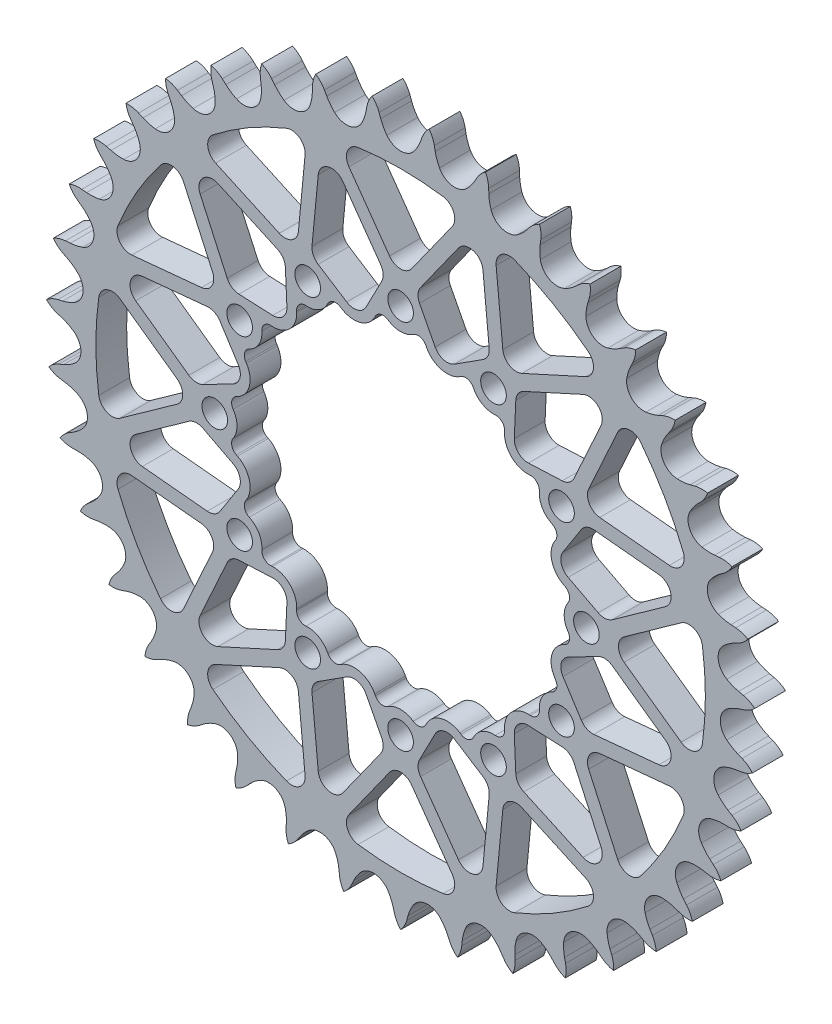
SolidWorks part; units mm, degrees
material "7075-T6 (SN)"
ref_plane "Front Plane" through (0, 0, 0) normal (0, 0, 1) x (1, 0, 0)
ref_plane "Top Plane" through (0, 0, 0) normal (0, 1, 0) x (1, 0, 0)
ref_plane "Right Plane" through (0, 0, 0) normal (1, 0, 0) x (0, 0, -1)
sketch "Work Sketch" plane through (0, 0, 0) normal (0, 0, 1) x (1, 0, 0)
  line L0 (0, 0) -> (0, 160.4542) construction
  line L1 (-112.0919, 78.9148) -> (87.2579, 78.9148) construction
  line L2 (5.102, 120.8822) -> (5.102, 112.9699) construction
  line L3 (-12.8497, 82.6953) -> (16.7256, 82.6953) construction
  line L4 (5.102, 82.6953) -> (-6.0879, 74.4036) construction
  line L5 (5.102, 82.6953) -> (-4.6505, 79.1506) construction
  line L6 (-4.6505, 79.1506) -> (-6.8863, 85.3019)
  line L7 (-11.5114, 78.0206) -> (-7.1525, 78.0206) construction
  line L8 (-11.0765, 124.7602) -> (-11.0765, 110.2345) construction
  line L9 (0, 0) -> (-3.4402, 42.6146) construction
  circle A0 centre (0, 0) radius 78.9148
  circle A1 centre (0, 78.9148) radius 4.0088
  arc A2 (-4.6505, 79.1506) -> (-3.2209, 76.5281) centre (5.0804, 82.7541) ccw
  circle A3 centre (-11.0765, 78.0206) radius 6.4254
  point P23 (-3.2209, 76.5281)
  dimension "D1" = 157.8295
  dimension "D8" = 10.3767
  dimension "D2" = 8.0177
  dimension "D3" = 5.102
  dimension "D4" = 3.7806
  dimension "D5" = 36.538
  dimension "D6" = 16.564
  dimension "D7" = 10.3767
  dimension "D9" = 0.8942
  dimension "D10" = 11.0765
  dimension "D11" = 4.615
sketch "Teeth Sketch" plane through (0, 0, 0) normal (0, 0, 1) x (1, 0, 0)
  line L0 (5.0376, 80.2155) -> (4.6505, 79.1506)
  line L1 (-7.4865, 92.7372) -> (-4.7839, 59.2593) construction
  line L2 (0, 0) -> (-10.9133, 132.3061) construction
  line L3 (7.8951, 79.9848) -> (8.1063, 78.8717)
  line L4 (16093.3137, -199351.4616) -> (-16096.7539, 199394.0762) construction
  line L5 (0, 146.3285) -> (0, 56.9858) construction
  line L6 (17.8398, 78.3686) -> (17.287, 77.3797)
  line L7 (0, -200000) -> (0, 200160.4542) construction
  line L8 (20.6234, 77.6826) -> (20.6533, 76.5499)
  line L9 (-4.6505, 79.1506) -> (-6.8863, 85.3019) construction
  line L10 (44.1616, 67.154) -> (43.8313, 66.0702)
  line L11 (-5.0376, 80.2155) -> (-4.6505, 79.1506)
  line L12 (30.18, 74.4921) -> (29.4757, 73.6046)
  line L13 (32.8175, 73.3684) -> (32.6653, 72.2456)
  line L14 (41.7385, 68.6862) -> (40.901, 67.9232)
  line L15 (52.2161, 61.1014) -> (51.267, 60.4826)
  line L16 (54.362, 59.2003) -> (53.8621, 58.1836)
  line L17 (61.3413, 51.9341) -> (60.3052, 51.4756)
  line L18 (63.1544, 49.7134) -> (62.4979, 48.79)
  line L19 (68.8777, 41.4218) -> (67.7815, 41.1354)
  line L20 (70.3112, 38.939) -> (69.515, 38.1328)
  line L21 (74.6303, 29.8366) -> (73.5023, 29.7298)
  line L22 (75.6469, 27.156) -> (74.7318, 26.488)
  line L23 (78.45, 17.4787) -> (77.3195, 17.5542)
  line L24 (79.0234, 14.6698) -> (78.013, 14.1572)
  line L25 (80.2378, 4.6681) -> (79.1341, 4.9239)
  line L26 (80.3533, 1.8035) -> (79.2737, 1.4597)
  line L27 (79.9476, -8.2634) -> (78.8992, -7.8338)
  line L28 (79.602, -11.1094) -> (78.4813, -11.2756)
  line L29 (77.5867, -20.9809) -> (76.6208, -20.3887)
  line L30 (76.7891, -23.7346) -> (75.6562, -23.7189)
  line L31 (73.2164, -33.155) -> (72.358, -32.4155)
  line L32 (71.9874, -35.7451) -> (70.8717, -35.5478)
  line L33 (66.9499, -44.4704) -> (66.2212, -43.6028)
  line L34 (65.3213, -46.8298) -> (64.2517, -46.4561)
  line L35 (58.9493, -54.634) -> (58.3693, -53.6608)
  line L36 (56.9634, -56.7016) -> (55.9676, -56.1612)
  line L37 (49.422, -63.3827) -> (49.0056, -62.329)
  line L38 (47.1301, -65.1049) -> (46.2339, -64.4118)
  line L39 (38.6147, -70.4897) -> (38.3727, -69.3829)
  line L40 (36.0763, -71.822) -> (35.3028, -70.9941)
  line L41 (26.8073, -75.7712) -> (26.746, -74.6398)
  line L42 (24.088, -76.679) -> (23.4574, -75.7377)
  line L43 (14.3056, -79.0901) -> (14.4266, -77.9636)
  line L44 (11.4759, -79.55) -> (11.0044, -78.5198)
  line L45 (1.4334, -80.3607) -> (1.7335, -79.2682)
  line L46 (-1.4334, -80.3607) -> (-1.7335, -79.2682)
  line L47 (-11.4759, -79.55) -> (-11.0044, -78.5198)
  line L48 (-14.3056, -79.0901) -> (-14.4266, -77.9636)
  line L49 (-24.088, -76.679) -> (-23.4574, -75.7377)
  line L50 (-26.8073, -75.7712) -> (-26.746, -74.6398)
  line L51 (-36.0763, -71.822) -> (-35.3028, -70.9941)
  line L52 (-38.6147, -70.4897) -> (-38.3727, -69.3829)
  line L53 (-47.1301, -65.1049) -> (-46.2339, -64.4118)
  line L54 (-49.422, -63.3827) -> (-49.0056, -62.329)
  line L55 (-56.9634, -56.7016) -> (-55.9676, -56.1612)
  line L56 (-58.9493, -54.634) -> (-58.3693, -53.6608)
  line L57 (-65.3213, -46.8298) -> (-64.2517, -46.4561)
  line L58 (-66.9499, -44.4704) -> (-66.2212, -43.6028)
  line L59 (-71.9874, -35.7451) -> (-70.8717, -35.5478)
  line L60 (-73.2164, -33.155) -> (-72.358, -32.4155)
  line L61 (-76.7891, -23.7346) -> (-75.6562, -23.7189)
  line L62 (-77.5867, -20.9809) -> (-76.6208, -20.3887)
  line L63 (-79.602, -11.1094) -> (-78.4813, -11.2756)
  line L64 (-79.9476, -8.2634) -> (-78.8992, -7.8338)
  line L65 (-80.3533, 1.8035) -> (-79.2737, 1.4597)
  line L66 (-80.2378, 4.6681) -> (-79.1341, 4.9239)
  line L67 (-79.0234, 14.6698) -> (-78.013, 14.1572)
  line L68 (-78.45, 17.4787) -> (-77.3195, 17.5542)
  line L69 (-75.6469, 27.156) -> (-74.7318, 26.488)
  line L70 (-74.6303, 29.8366) -> (-73.5023, 29.7298)
  line L71 (-70.3112, 38.939) -> (-69.515, 38.1328)
  line L72 (-68.8777, 41.4218) -> (-67.7815, 41.1354)
  line L73 (-63.1544, 49.7134) -> (-62.4979, 48.79)
  line L74 (-61.3413, 51.9341) -> (-60.3052, 51.4756)
  line L75 (-54.362, 59.2003) -> (-53.8621, 58.1836)
  line L76 (-52.2161, 61.1014) -> (-51.267, 60.4826)
  line L77 (-44.1616, 67.154) -> (-43.8313, 66.0702)
  line L78 (-41.7385, 68.6862) -> (-40.901, 67.9232)
  line L79 (-32.8175, 73.3684) -> (-32.6653, 72.2456)
  line L80 (-30.18, 74.4921) -> (-29.4757, 73.6046)
  line L81 (-20.6234, 77.6826) -> (-20.6533, 76.5499)
  line L82 (-17.8398, 78.3686) -> (-17.287, 77.3797)
  line L83 (-7.8951, 79.9848) -> (-8.1063, 78.8717)
  arc A0 (-6.8336, 82.8459) -> (-5.0376, 80.2155) centre (-11.0765, 78.0206) cw
  circle A1 centre (-11.0765, 78.0206) radius 6.4254 construction
  arc A2 (-3.2209, 76.5281) -> (-4.6505, 79.1506) centre (5.0804, 82.7541) cw
  arc A3 (-4.6505, 79.1506) -> (-3.2209, 76.5281) centre (5.0804, 82.7541) ccw construction
  circle A4 centre (0, 78.9148) radius 4.0088 construction
  arc A5 (-3.2209, 76.5281) -> (3.2209, 76.5281) centre (0, 78.9148) ccw
  arc A6 (3.2209, 76.5281) -> (4.6505, 79.1506) centre (-5.0804, 82.7541) ccw
  arc A7 (6.8336, 82.8459) -> (5.0376, 80.2155) centre (11.0765, 78.0206) ccw
  arc A8 (6.5443, 82.8692) -> (7.8951, 79.9848) centre (1.5824, 78.787) cw
  arc A9 (9.0967, 76.0537) -> (8.1063, 78.8717) centre (18.2893, 80.8676) cw
  arc A10 (9.0967, 76.0537) -> (15.4552, 75.0204) centre (12.6588, 77.8928) ccw
  arc A11 (15.4552, 75.0204) -> (17.287, 77.3797) centre (8.2601, 82.4975) ccw
  arc A12 (20.0345, 80.6769) -> (17.8398, 78.3686) centre (23.4484, 75.2334) ccw
  arc A13 (19.7528, 80.7463) -> (20.6234, 77.6826) centre (14.2002, 77.5129) cw
  arc A14 (21.1788, 73.6096) -> (20.6533, 76.5499) centre (31.0245, 76.8865) cw
  arc A15 (21.1788, 73.6096) -> (27.2892, 71.5697) centre (24.9898, 74.8535) ccw
  arc A16 (27.2892, 71.5697) -> (29.4757, 73.6046) centre (21.3867, 80.1041) ccw
  arc A17 (32.7165, 76.4184) -> (30.18, 74.4921) centre (35.2131, 70.4978) ccw
  arc A18 (32.4496, 76.5321) -> (32.8175, 73.3684) centre (26.4502, 74.2313) cw
  arc A19 (32.7124, 69.2591) -> (32.6653, 72.2456) centre (42.9562, 70.9142) cw
  arc A20 (32.7124, 69.2591) -> (38.4163, 66.2654) centre (36.6735, 69.8756) ccw
  arc A21 (38.4163, 66.2654) -> (40.901, 67.9232) centre (33.9593, 75.6361) ccw
  arc A22 (44.5512, 70.1807) -> (41.7385, 68.6862) centre (46.0657, 63.9363) ccw
  arc A23 (44.306, 70.3358) -> (44.1616, 67.154) centre (38.0153, 69.0271) cw
  arc A24 (43.3987, 63.1147) -> (43.8313, 66.0702) centre (53.7754, 63.1052) cw
  arc A25 (43.3987, 63.1147) -> (48.5486, 59.2448) centre (47.4074, 63.0878) ccw
  arc A26 (48.5486, 59.2448) -> (51.267, 60.4826) centre (45.6524, 69.2092) ccw
  arc A27 (55.2321, 62.1253) -> (52.2161, 61.1014) centre (55.7253, 55.7189) ccw
  arc A28 (55.0149, 62.3178) -> (54.362, 59.2003) centre (48.5957, 62.0351) cw
  arc A29 (52.961, 55.3358) -> (53.8621, 58.1836) centre (63.2018, 53.6618) cw
  arc A30 (52.961, 55.3358) -> (57.4234, 50.6899) centre (56.9135, 54.6662) ccw
  arc A31 (57.4234, 50.6899) -> (60.3052, 51.4756) centre (56.1632, 60.9898) ccw
  arc A32 (64.4824, 52.461) -> (61.3413, 51.9341) centre (63.9416, 46.0584) ccw
  arc A33 (64.2989, 52.6858) -> (63.1544, 49.7134) centre (57.9175, 53.4365) cw
  arc A34 (61.1517, 46.1237) -> (62.4979, 48.79) centre (70.9913, 42.8287) cw
  arc A35 (61.1517, 46.1237) -> (64.811, 40.8221) centre (64.9456, 44.8287) ccw
  arc A36 (64.811, 40.8221) -> (67.7815, 41.1354) centre (65.2193, 51.1908) ccw
  arc A37 (72.0627, 41.4379) -> (68.8777, 41.4218) centre (70.5018, 35.205) ccw
  arc A38 (71.9177, 41.6892) -> (70.3112, 38.939) centre (65.7393, 43.4539) cw
  arc A39 (67.7585, 35.717) -> (69.515, 38.1328) centre (76.9422, 30.8862) cw
  arc A40 (67.7585, 35.717) -> (70.5201, 29.8971) centre (71.2956, 33.8302) ccw
  arc A41 (70.5201, 29.8971) -> (73.5023, 29.7298) centre (72.5864, 40.0659) ccw
  arc A42 (77.7767, 29.3416) -> (74.6303, 29.8366) centre (75.2361, 23.4398) ccw
  arc A43 (77.6738, 29.6129) -> (75.6469, 27.156) centre (71.8585, 32.3458) cw
  arc A44 (72.6105, 24.3852) -> (74.7318, 26.488) centre (80.9003, 18.1439) cw
  arc A45 (72.6105, 24.3852) -> (74.4027, 18.1977) centre (75.7991, 21.9555) ccw
  arc A46 (74.4027, 18.1977) -> (77.3195, 17.5542) centre (78.0734, 27.9034) ccw
  arc A47 (81.4762, 16.4854) -> (78.45, 17.4787) centre (78.0218, 11.0675) ccw
  arc A48 (81.4182, 16.7697) -> (79.0234, 14.6698) centre (76.1166, 20.4) cw
  arc A49 (75.5818, 12.4219) -> (78.013, 14.1572) centre (82.7631, 4.9316) cw
  arc A50 (75.5818, 12.4219) -> (76.3583, 6.027) centre (78.3394, 9.5121) ccw
  arc A51 (76.3583, 6.027) -> (79.1341, 4.9239) centre (81.5384, 15.0182) ccw
  arc A52 (83.0656, 3.2022) -> (80.2378, 4.6681) centre (78.7868, -1.5914) ccw
  arc A53 (83.0539, 3.4922) -> (80.3533, 1.8035) centre (78.4033, 7.9259) cw
  arc A54 (76.5957, 0.1368) -> (79.2737, 1.4597) centre (82.4825, -8.4084) cw
  arc A55 (76.5957, 0.1368) -> (76.3363, -6.2998) centre (78.8508, -3.1776) ccw
  arc A56 (76.3363, -6.2998) -> (78.8992, -7.8338) centre (82.8916, 1.7441) ccw
  arc A57 (82.5035, -10.1639) -> (79.9476, -8.2634) centre (77.5113, -14.2091) ccw
  arc A58 (82.5385, -9.8758) -> (79.602, -11.1094) centre (78.6594, -4.7535) cw
  arc A59 (75.6257, -12.1517) -> (78.4813, -11.2756) centre (80.0655, -21.5307) cw
  arc A60 (75.6257, -12.1517) -> (74.3372, -18.4634) centre (77.3199, -15.785) ccw
  arc A61 (74.3372, -18.4634) -> (76.6208, -20.3887) centre (82.0979, -11.5753) ccw
  arc A62 (79.8047, -23.2668) -> (77.5867, -20.9809) centre (74.2283, -26.4587) ccw
  arc A63 (79.8855, -22.9881) -> (76.7891, -23.7346) centre (76.8783, -17.3098) cw
  arc A64 (72.6971, -24.1256) -> (75.6562, -23.7189) centre (75.5749, -34.0953) cw
  arc A65 (72.6971, -24.1256) -> (70.4128, -30.1488) centre (73.7866, -27.9836) ccw
  arc A66 (70.4128, -30.1488) -> (72.358, -32.4155) centre (79.178, -24.5948) ccw
  arc A67 (75.039, -35.7671) -> (73.2164, -33.155) centre (69.0227, -38.0232) ccw
  arc A68 (75.1634, -35.5049) -> (71.9874, -35.7451) centre (73.106, -29.4178) cw
  arc A69 (67.8857, -35.4746) -> (70.8717, -35.5478) centre (69.127, -45.7768) cw
  arc A70 (67.8857, -35.4746) -> (64.6648, -41.0534) centre (68.3422, -39.4574) ccw
  arc A71 (64.6648, -41.0534) -> (66.2212, -43.6028) centre (74.2074, -36.9773) ccw
  arc A72 (68.3299, -47.341) -> (66.9499, -44.4704) centre (62.0296, -48.6028) ccw
  arc A73 (68.4947, -47.1022) -> (65.3213, -46.8298) centre (67.4404, -40.7639) cw
  arc A74 (61.3161, -45.9049) -> (64.2517, -46.4561) centre (60.8887, -56.2728) cw
  arc A75 (61.3161, -45.9049) -> (57.2419, -50.8948) centre (61.1278, -49.9093) ccw
  arc A76 (57.2419, -50.8948) -> (58.3693, -53.6608) centre (67.3148, -48.4022) ccw
  arc A77 (59.851, -57.6888) -> (58.9493, -54.634) centre (53.4299, -57.9236) ccw
  arc A78 (60.052, -57.4796) -> (56.9634, -56.7016) centre (60.0281, -51.0542) cw
  arc A79 (53.1584, -55.1462) -> (55.9676, -56.1612) centre (51.0734, -65.3113) cw
  arc A80 (53.1584, -55.1462) -> (48.3366, -59.4179) centre (52.3302, -59.0685) ccw
  arc A81 (48.3366, -59.4179) -> (49.0056, -62.329) centre (58.6789, -58.5735) ccw
  arc A82 (49.822, -66.5425) -> (49.422, -63.3827) centre (43.4464, -65.7443) ccw
  arc A83 (50.054, -66.3682) -> (47.1301, -65.1049) centre (51.0611, -60.0222) cw
  arc A84 (43.6239, -62.9593) -> (46.2339, -64.4118) centre (39.9354, -72.6583) cw
  arc A85 (43.6239, -62.9593) -> (38.1793, -66.4022) centre (42.1772, -66.698) ccw
  arc A86 (38.1793, -66.4022) -> (38.3727, -69.3829) centre (48.5231, -67.2277) ccw
  arc A87 (38.5026, -73.6728) -> (38.6147, -70.4897) centre (32.3376, -71.8622) ccw
  arc A88 (38.7596, -73.538) -> (36.0763, -71.822) centre (40.7716, -67.4357) cw
  arc A89 (32.9596, -69.1417) -> (35.3028, -70.9941) centre (27.763, -78.1234) cw
  arc A90 (32.9596, -69.1417) -> (27.0333, -71.6667) centre (30.932, -72.6) ccw
  arc A91 (27.0333, -71.6667) -> (26.746, -74.6398) centre (37.1107, -74.1408) ccw
  arc A92 (26.1861, -78.8951) -> (26.8073, -75.7712) centre (20.3913, -76.1189) ccw
  arc A93 (26.4613, -78.8032) -> (24.088, -76.679) centre (29.4261, -73.1027) cw
  arc A94 (21.4417, -73.5335) -> (23.4574, -75.7377) centre (14.8716, -81.5653) cw
  arc A95 (21.4417, -73.5335) -> (15.187, -75.0751) centre (18.8855, -76.6216) ccw
  arc A96 (15.187, -75.0751) -> (14.4266, -77.9636) centre (24.7371, -79.1336) ccw
  arc A97 (13.1913, -82.0739) -> (14.3056, -79.0901) centre (7.9169, -78.4042) ccw
  arc A98 (13.4777, -82.0274) -> (11.4759, -79.55) centre (17.3186, -76.8763) cw
  arc A99 (9.3684, -76.0207) -> (11.0044, -78.5198) centre (1.595, -82.8946) cw
  arc A100 (9.3684, -76.0207) -> (2.9475, -76.5391) centre (6.35, -78.6589) ccw
  arc A101 (2.9475, -76.5391) -> (1.7335, -79.2682) centre (11.7228, -82.077) ccw
  arc A102 (-0.1451, -83.1271) -> (1.4334, -80.3607) centre (-4.7625, -78.6589) ccw
  arc A103 (0.1451, -83.1271) -> (-1.4334, -80.3607) centre (4.7625, -78.6589) cw
  arc A104 (-2.9475, -76.5391) -> (-1.7335, -79.2682) centre (-11.7228, -82.077) cw
  arc A105 (-2.9475, -76.5391) -> (-9.3684, -76.0207) centre (-6.35, -78.6589) ccw
  arc A106 (-9.3684, -76.0207) -> (-11.0044, -78.5198) centre (-1.595, -82.8946) ccw
  arc A107 (-13.4777, -82.0274) -> (-11.4759, -79.55) centre (-17.3186, -76.8763) ccw
  arc A108 (-13.1913, -82.0739) -> (-14.3056, -79.0901) centre (-7.9169, -78.4042) cw
  arc A109 (-15.187, -75.0751) -> (-14.4266, -77.9636) centre (-24.7371, -79.1336) cw
  arc A110 (-15.187, -75.0751) -> (-21.4417, -73.5335) centre (-18.8855, -76.6216) ccw
  arc A111 (-21.4417, -73.5335) -> (-23.4574, -75.7377) centre (-14.8716, -81.5653) ccw
  arc A112 (-26.4613, -78.8032) -> (-24.088, -76.679) centre (-29.4261, -73.1027) ccw
  arc A113 (-26.1861, -78.8951) -> (-26.8073, -75.7712) centre (-20.3913, -76.1189) cw
  arc A114 (-27.0333, -71.6667) -> (-26.746, -74.6398) centre (-37.1107, -74.1408) cw
  arc A115 (-27.0333, -71.6667) -> (-32.9596, -69.1417) centre (-30.932, -72.6) ccw
  arc A116 (-32.9596, -69.1417) -> (-35.3028, -70.9941) centre (-27.763, -78.1234) ccw
  arc A117 (-38.7596, -73.538) -> (-36.0763, -71.822) centre (-40.7716, -67.4357) ccw
  arc A118 (-38.5026, -73.6728) -> (-38.6147, -70.4897) centre (-32.3376, -71.8622) cw
  arc A119 (-38.1793, -66.4022) -> (-38.3727, -69.3829) centre (-48.5231, -67.2277) cw
  arc A120 (-38.1793, -66.4022) -> (-43.6239, -62.9593) centre (-42.1772, -66.698) ccw
  arc A121 (-43.6239, -62.9593) -> (-46.2339, -64.4118) centre (-39.9354, -72.6583) ccw
  arc A122 (-50.054, -66.3682) -> (-47.1301, -65.1049) centre (-51.0611, -60.0222) ccw
  arc A123 (-49.822, -66.5425) -> (-49.422, -63.3827) centre (-43.4464, -65.7443) cw
  arc A124 (-48.3366, -59.4179) -> (-49.0056, -62.329) centre (-58.6789, -58.5735) cw
  arc A125 (-48.3366, -59.4179) -> (-53.1584, -55.1462) centre (-52.3302, -59.0685) ccw
  arc A126 (-53.1584, -55.1462) -> (-55.9676, -56.1612) centre (-51.0734, -65.3113) ccw
  arc A127 (-60.052, -57.4796) -> (-56.9634, -56.7016) centre (-60.0281, -51.0542) ccw
  arc A128 (-59.851, -57.6888) -> (-58.9493, -54.634) centre (-53.4299, -57.9236) cw
  arc A129 (-57.2419, -50.8948) -> (-58.3693, -53.6608) centre (-67.3148, -48.4022) cw
  arc A130 (-57.2419, -50.8948) -> (-61.3161, -45.9049) centre (-61.1278, -49.9093) ccw
  arc A131 (-61.3161, -45.9049) -> (-64.2517, -46.4561) centre (-60.8887, -56.2728) ccw
  arc A132 (-68.4947, -47.1022) -> (-65.3213, -46.8298) centre (-67.4404, -40.7639) ccw
  arc A133 (-68.3299, -47.341) -> (-66.9499, -44.4704) centre (-62.0296, -48.6028) cw
  arc A134 (-64.6648, -41.0534) -> (-66.2212, -43.6028) centre (-74.2074, -36.9773) cw
  arc A135 (-64.6648, -41.0534) -> (-67.8857, -35.4746) centre (-68.3422, -39.4574) ccw
  arc A136 (-67.8857, -35.4746) -> (-70.8717, -35.5478) centre (-69.127, -45.7768) ccw
  arc A137 (-75.1634, -35.5049) -> (-71.9874, -35.7451) centre (-73.106, -29.4178) ccw
  arc A138 (-75.039, -35.7671) -> (-73.2164, -33.155) centre (-69.0227, -38.0232) cw
  arc A139 (-70.4128, -30.1488) -> (-72.358, -32.4155) centre (-79.178, -24.5948) cw
  arc A140 (-70.4128, -30.1488) -> (-72.6971, -24.1256) centre (-73.7866, -27.9836) ccw
  arc A141 (-72.6971, -24.1256) -> (-75.6562, -23.7189) centre (-75.5749, -34.0953) ccw
  arc A142 (-79.8855, -22.9881) -> (-76.7891, -23.7346) centre (-76.8783, -17.3098) ccw
  arc A143 (-79.8047, -23.2668) -> (-77.5867, -20.9809) centre (-74.2283, -26.4587) cw
  arc A144 (-74.3372, -18.4634) -> (-76.6208, -20.3887) centre (-82.0979, -11.5753) cw
  arc A145 (-74.3372, -18.4634) -> (-75.6257, -12.1517) centre (-77.3199, -15.785) ccw
  arc A146 (-75.6257, -12.1517) -> (-78.4813, -11.2756) centre (-80.0655, -21.5307) ccw
  arc A147 (-82.5385, -9.8758) -> (-79.602, -11.1094) centre (-78.6594, -4.7535) ccw
  arc A148 (-82.5035, -10.1639) -> (-79.9476, -8.2634) centre (-77.5113, -14.2091) cw
  arc A149 (-76.3363, -6.2998) -> (-78.8992, -7.8338) centre (-82.8916, 1.7441) cw
  arc A150 (-76.3363, -6.2998) -> (-76.5957, 0.1368) centre (-78.8508, -3.1776) ccw
  arc A151 (-76.5957, 0.1368) -> (-79.2737, 1.4597) centre (-82.4825, -8.4084) ccw
  arc A152 (-83.0539, 3.4922) -> (-80.3533, 1.8035) centre (-78.4033, 7.9259) ccw
  arc A153 (-83.0656, 3.2022) -> (-80.2378, 4.6681) centre (-78.7868, -1.5914) cw
  arc A154 (-76.3583, 6.027) -> (-79.1341, 4.9239) centre (-81.5384, 15.0182) cw
  arc A155 (-76.3583, 6.027) -> (-75.5818, 12.4219) centre (-78.3394, 9.5121) ccw
  arc A156 (-75.5818, 12.4219) -> (-78.013, 14.1572) centre (-82.7631, 4.9316) ccw
  arc A157 (-81.4182, 16.7697) -> (-79.0234, 14.6698) centre (-76.1166, 20.4) ccw
  arc A158 (-81.4762, 16.4854) -> (-78.45, 17.4787) centre (-78.0218, 11.0675) cw
  arc A159 (-74.4027, 18.1977) -> (-77.3195, 17.5542) centre (-78.0734, 27.9034) cw
  arc A160 (-74.4027, 18.1977) -> (-72.6105, 24.3852) centre (-75.7991, 21.9555) ccw
  arc A161 (-72.6105, 24.3852) -> (-74.7318, 26.488) centre (-80.9003, 18.1439) ccw
  arc A162 (-77.6738, 29.6129) -> (-75.6469, 27.156) centre (-71.8585, 32.3458) ccw
  arc A163 (-77.7767, 29.3416) -> (-74.6303, 29.8366) centre (-75.2361, 23.4398) cw
  arc A164 (-70.5201, 29.8971) -> (-73.5023, 29.7298) centre (-72.5864, 40.0659) cw
  arc A165 (-70.5201, 29.8971) -> (-67.7585, 35.717) centre (-71.2956, 33.8302) ccw
  arc A166 (-67.7585, 35.717) -> (-69.515, 38.1328) centre (-76.9422, 30.8862) ccw
  arc A167 (-71.9177, 41.6892) -> (-70.3112, 38.939) centre (-65.7393, 43.4539) ccw
  arc A168 (-72.0627, 41.4379) -> (-68.8777, 41.4218) centre (-70.5018, 35.205) cw
  arc A169 (-64.811, 40.8221) -> (-67.7815, 41.1354) centre (-65.2193, 51.1908) cw
  arc A170 (-64.811, 40.8221) -> (-61.1517, 46.1237) centre (-64.9456, 44.8287) ccw
  arc A171 (-61.1517, 46.1237) -> (-62.4979, 48.79) centre (-70.9913, 42.8287) ccw
  arc A172 (-64.2989, 52.6858) -> (-63.1544, 49.7134) centre (-57.9175, 53.4365) ccw
  arc A173 (-64.4824, 52.461) -> (-61.3413, 51.9341) centre (-63.9416, 46.0584) cw
  arc A174 (-57.4234, 50.6899) -> (-60.3052, 51.4756) centre (-56.1632, 60.9898) cw
  arc A175 (-57.4234, 50.6899) -> (-52.961, 55.3358) centre (-56.9135, 54.6662) ccw
  arc A176 (-52.961, 55.3358) -> (-53.8621, 58.1836) centre (-63.2018, 53.6618) ccw
  arc A177 (-55.0149, 62.3178) -> (-54.362, 59.2003) centre (-48.5957, 62.0351) ccw
  arc A178 (-55.2321, 62.1253) -> (-52.2161, 61.1014) centre (-55.7253, 55.7189) cw
  arc A179 (-48.5486, 59.2448) -> (-51.267, 60.4826) centre (-45.6524, 69.2092) cw
  arc A180 (-48.5486, 59.2448) -> (-43.3987, 63.1147) centre (-47.4074, 63.0878) ccw
  arc A181 (-43.3987, 63.1147) -> (-43.8313, 66.0702) centre (-53.7754, 63.1052) ccw
  arc A182 (-44.306, 70.3358) -> (-44.1616, 67.154) centre (-38.0153, 69.0271) ccw
  arc A183 (-44.5512, 70.1807) -> (-41.7385, 68.6862) centre (-46.0657, 63.9363) cw
  arc A184 (-38.4163, 66.2654) -> (-40.901, 67.9232) centre (-33.9593, 75.6361) cw
  arc A185 (-38.4163, 66.2654) -> (-32.7124, 69.2591) centre (-36.6735, 69.8756) ccw
  arc A186 (-32.7124, 69.2591) -> (-32.6653, 72.2456) centre (-42.9562, 70.9142) ccw
  arc A187 (-32.4496, 76.5321) -> (-32.8175, 73.3684) centre (-26.4502, 74.2313) ccw
  arc A188 (-32.7165, 76.4184) -> (-30.18, 74.4921) centre (-35.2131, 70.4978) cw
  arc A189 (-27.2892, 71.5697) -> (-29.4757, 73.6046) centre (-21.3867, 80.1041) cw
  arc A190 (-27.2892, 71.5697) -> (-21.1788, 73.6096) centre (-24.9898, 74.8535) ccw
  arc A191 (-21.1788, 73.6096) -> (-20.6533, 76.5499) centre (-31.0245, 76.8865) ccw
  arc A192 (-19.7528, 80.7463) -> (-20.6234, 77.6826) centre (-14.2002, 77.5129) ccw
  arc A193 (-20.0345, 80.6769) -> (-17.8398, 78.3686) centre (-23.4484, 75.2334) cw
  arc A194 (-15.4552, 75.0204) -> (-17.287, 77.3797) centre (-8.2601, 82.4975) cw
  arc A195 (-15.4552, 75.0204) -> (-9.0967, 76.0537) centre (-12.6588, 77.8928) ccw
  arc A196 (-9.0967, 76.0537) -> (-8.1063, 78.8717) centre (-18.2893, 80.8676) ccw
  arc A197 (-6.5443, 82.8692) -> (-7.8951, 79.9848) centre (-1.5824, 78.787) ccw
  point P77 (0, 0)
  dimension "D1" = 4.615
  dimension "D2" = 4.715
  dimension "D3" = 39
extrude "Extrusion" add sketch "Teeth Sketch" along normal blind 7.2136 contours A0 region at (0, 0, 0)
sketch "Sketch1" plane through (0, 0, 0) normal (0, 0, -1) x (-1, 0, 0)
  circle A0 centre (0, 0) radius 78.9443
  circle A1 centre (0, 0) radius 35.7643
  dimension "D1" = 43.18
extrude "Cut-Extrude" cut sketch "Sketch1" against normal through all both and the other way through all contours A1
ref_axis "Axis1" [suppressed] through (0, 0, 7.2136) along (0, 0, -1)
ref_plane "Sprocket Center Plane" through (0, 0, 3.6068) normal (0, 0, 1) x (1, 0, 0)
sketch "Pitch Circle" plane through (0, 0, 3.6068) normal (0, 0, -1) x (-1, 0, 0)
  circle A0 centre (0, 0) radius 82.9531 construction
  dimension "D1" = 165.9063
sketch "Chain Pitch Circle" plane through (0, 0, 0) normal (0, 0, -1) x (-1, 0, 0)
  circle A0 centre (0, 0) radius 82.9531 construction
  dimension "D1" = 165.9063
ref_plane "Center Plane" through (0, 0, 3.6068) normal (0, 0, 1) x (1, 0, 0)
hole_wizard "Ø6.0mm Dowel Hole1" positions "Sketch7" profile "Sketch8" hole size "Ø6.0" standard "ANSI Metric" end condition through all
sketch "Sketch7" plane through (0, 0, 7.2136) normal (0, 0, 1) x (1, 0, 0)
  point P0 (-43.5, 0)
  dimension "D1" = 43.5
sketch "Sketch8" plane through (-43.5, 0, 7.2136) normal (1, 0, 0) x (0, -1, 0)
  line L0 (0, 0) -> (0, 7.2136)
  line L1 (0, 7.2136) -> (3, 7.2136)
  line L2 (3, 7.2136) -> (3, 0)
  line L5 (3, 0) -> (0, 0)
  line L11 (0, -6.35) -> (0, 107.95) construction
  dimension "Thru Hole Dia." = 6
  dimension "Thru Hole Depth" = 7.2136
pattern_circular "CirPattern1" count 12 over 360 about axis through (0, 0, 7.2136) along (0, 0, -1) of "Ø6.0mm Dowel Hole1" reverse direction yes
ref_plane "Plane1" through (0, 0, 3.6068) normal (0, 0, -1) x (-1, 0, 0)
sketch "Sketch9" plane through (0, 0, 0) normal (0, 0, 1) x (1, 0, 0)
  line L0 (-43.5, 0) -> (-71.3499, 0) construction
  line L1 (-69.7539, 15.0068) -> (-48.707, 0)
  line L2 (-69.7539, -15.0068) -> (-48.707, 0)
  line L11 (-43.5, 0) -> (-37.6721, 21.75) construction
  line L13 (-68.9187, 18.4667) -> (-36.1404, 9.6838) construction
  line L18 (-43.3252, 20.9264) -> (-36.1404, 9.6838)
  line L19 (-47.9839, 3.5399) -> (-36.1404, 9.6838)
  line L20 (-43.3252, 20.9264) -> (-68.9187, 18.4667)
  line L21 (-47.9839, 3.5399) -> (-68.9187, 18.4667)
  circle A0 centre (0, 0) radius 74.9059 construction
  arc A1 (-57.4234, 50.6899) -> (-52.961, 55.3358) centre (-56.9135, 54.6662) ccw construction
  circle A2 centre (-43.5, 0) radius 3 construction
  circle A3 centre (-43.5, 0) radius 5.207
  circle A4 centre (-37.6721, 21.75) radius 3 construction
  circle A6 centre (-37.6721, 21.75) radius 5.207
  circle A196 centre (0, 0) radius 71.3499
  circle A197 centre (0, 0) radius 35.7643 construction
  circle A198 centre (0, 0) radius 35.7643
  circle A199 centre (0, 0) radius 37.4153 construction
  point P17 (-40.5861, 10.875)
  dimension "D1" = 3.556
  dimension "D2" = 1.651
  dimension "D3" = 10.414
  dimension "D4" = 3.302
extrude "Cut-Extrude2" cut sketch "Sketch9" along normal through all contours L1 A196 L2 | L21 L19 L18 L20 region at (-63.4426, 0, 0) region at (-50.2379, 13.4612, 0)
fillet "Fillet2" radius 3.175 7 edges at (-68.9187, 18.4667, 3.6068) (-36.1404, 9.6838, 3.6068) (-47.9839, 3.5399, 3.6068) (-43.3252, 20.9264, 3.6068) (-69.7539, -15.0068, 3.6068) (-48.707, 0, 3.6068) (-69.7539, 15.0068, 3.6068)
pattern_circular "CirPattern3" count 12 over 360 about axis through (0, 0, 7.2136) along (0, 0, -1) of "Cut-Extrude2", "Fillet2"
sketch "Sketch14" plane through (0, 0, 7.2136) normal (0, 0, 1) x (1, 0, 0)
  line L0 (-46.26, -4.4342) -> (-39.2249, -8.0837) construction
  line L1 (-38.1722, 6.0545) -> (-38.4679, 5.9011)
  line L2 (-43.5, 0) -> (-38.293, 0) construction
  line L3 (-38.1722, -6.0545) -> (-38.4679, -5.9011)
  line L4 (-30.0309, 24.3294) -> (-30.3636, 24.3444)
  line L5 (-36.0854, 13.8428) -> (-36.2647, 14.1234)
  line L6 (-13.8428, 36.0854) -> (-14.1234, 36.2647)
  line L7 (-24.3294, 30.0309) -> (-24.3444, 30.3636)
  line L8 (6.0545, 38.1722) -> (5.9011, 38.4679)
  line L9 (-6.0545, 38.1722) -> (-5.9011, 38.4679)
  line L10 (24.3294, 30.0309) -> (24.3444, 30.3636)
  line L11 (13.8428, 36.0854) -> (14.1234, 36.2647)
  line L12 (36.0854, 13.8428) -> (36.2647, 14.1234)
  line L13 (30.0309, 24.3294) -> (30.3636, 24.3444)
  line L14 (38.1722, -6.0545) -> (38.4679, -5.9011)
  line L15 (38.1722, 6.0545) -> (38.4679, 5.9011)
  line L16 (30.0309, -24.3294) -> (30.3636, -24.3444)
  line L17 (36.0854, -13.8428) -> (36.2647, -14.1234)
  line L18 (13.8428, -36.0854) -> (14.1234, -36.2647)
  line L19 (24.3294, -30.0309) -> (24.3444, -30.3636)
  line L20 (-6.0545, -38.1722) -> (-5.9011, -38.4679)
  line L21 (6.0545, -38.1722) -> (5.9011, -38.4679)
  line L22 (-24.3294, -30.0309) -> (-24.3444, -30.3636)
  line L23 (-13.8428, -36.0854) -> (-14.1234, -36.2647)
  line L24 (-36.0854, -13.8428) -> (-36.2647, -14.1234)
  line L25 (-30.0309, -24.3294) -> (-30.3636, -24.3444)
  arc A0 (-39.2074, -2.9472) -> (-39.2074, 2.9472) centre (-43.5, 0) ccw
  circle A1 centre (0, 0) radius 35.7643 construction
  arc A2 (-38.4679, -5.9011) -> (-39.2074, -2.9472) centre (-37.5322, -4.0974) cw
  arc A3 (-38.1722, 6.0545) -> (-36.0854, 13.8428) centre (-40.6869, 10.902) ccw
  arc A4 (-38.1722, 6.0545) -> (-36.0854, 13.8428) centre (-40.6869, 10.902) ccw
  arc A5 (-38.4679, 5.9011) -> (-39.2074, 2.9472) centre (-37.5322, 4.0974) ccw
  circle A6 centre (0, 0) radius 35.7643
  arc A7 (-30.0309, 24.3294) -> (-24.3294, 30.0309) centre (-29.7849, 29.7849) ccw
  arc A8 (-30.3636, 24.3444) -> (-32.481, 22.156) centre (-30.4551, 22.3145) ccw
  arc A9 (-35.4282, 17.0513) -> (-32.481, 22.156) centre (-37.6721, 21.75) ccw
  arc A10 (-36.2647, 14.1234) -> (-35.4282, 17.0513) centre (-34.5525, 15.2177) cw
  arc A11 (-13.8428, 36.0854) -> (-6.0545, 38.1722) centre (-10.902, 40.6869) ccw
  arc A12 (-14.1234, 36.2647) -> (-17.0513, 35.4282) centre (-15.2177, 34.5525) ccw
  arc A13 (-22.156, 32.481) -> (-17.0513, 35.4282) centre (-21.75, 37.6721) ccw
  arc A14 (-24.3444, 30.3636) -> (-22.156, 32.481) centre (-22.3145, 30.4551) cw
  arc A15 (6.0545, 38.1722) -> (13.8428, 36.0854) centre (10.902, 40.6869) ccw
  arc A16 (5.9011, 38.4679) -> (2.9472, 39.2074) centre (4.0974, 37.5322) ccw
  arc A17 (-2.9472, 39.2074) -> (2.9472, 39.2074) centre (0, 43.5) ccw
  arc A18 (-5.9011, 38.4679) -> (-2.9472, 39.2074) centre (-4.0974, 37.5322) cw
  arc A19 (24.3294, 30.0309) -> (30.0309, 24.3294) centre (29.7849, 29.7849) ccw
  arc A20 (24.3444, 30.3636) -> (22.156, 32.481) centre (22.3145, 30.4551) ccw
  arc A21 (17.0513, 35.4282) -> (22.156, 32.481) centre (21.75, 37.6721) ccw
  arc A22 (14.1234, 36.2647) -> (17.0513, 35.4282) centre (15.2177, 34.5525) cw
  arc A23 (36.0854, 13.8428) -> (38.1722, 6.0545) centre (40.6869, 10.902) ccw
  arc A24 (36.2647, 14.1234) -> (35.4282, 17.0513) centre (34.5525, 15.2177) ccw
  arc A25 (32.481, 22.156) -> (35.4282, 17.0513) centre (37.6721, 21.75) ccw
  arc A26 (30.3636, 24.3444) -> (32.481, 22.156) centre (30.4551, 22.3145) cw
  arc A27 (38.1722, -6.0545) -> (36.0854, -13.8428) centre (40.6869, -10.902) ccw
  arc A28 (38.4679, -5.9011) -> (39.2074, -2.9472) centre (37.5322, -4.0974) ccw
  arc A29 (39.2074, 2.9472) -> (39.2074, -2.9472) centre (43.5, 0) ccw
  arc A30 (38.4679, 5.9011) -> (39.2074, 2.9472) centre (37.5322, 4.0974) cw
  arc A31 (30.0309, -24.3294) -> (24.3294, -30.0309) centre (29.7849, -29.7849) ccw
  arc A32 (30.3636, -24.3444) -> (32.481, -22.156) centre (30.4551, -22.3145) ccw
  arc A33 (35.4282, -17.0513) -> (32.481, -22.156) centre (37.6721, -21.75) ccw
  arc A34 (36.2647, -14.1234) -> (35.4282, -17.0513) centre (34.5525, -15.2177) cw
  arc A35 (13.8428, -36.0854) -> (6.0545, -38.1722) centre (10.902, -40.6869) ccw
  arc A36 (14.1234, -36.2647) -> (17.0513, -35.4282) centre (15.2177, -34.5525) ccw
  arc A37 (22.156, -32.481) -> (17.0513, -35.4282) centre (21.75, -37.6721) ccw
  arc A38 (24.3444, -30.3636) -> (22.156, -32.481) centre (22.3145, -30.4551) cw
  arc A39 (-6.0545, -38.1722) -> (-13.8428, -36.0854) centre (-10.902, -40.6869) ccw
  arc A40 (-5.9011, -38.4679) -> (-2.9472, -39.2074) centre (-4.0974, -37.5322) ccw
  arc A41 (2.9472, -39.2074) -> (-2.9472, -39.2074) centre (0, -43.5) ccw
  arc A42 (5.9011, -38.4679) -> (2.9472, -39.2074) centre (4.0974, -37.5322) cw
  arc A43 (-24.3294, -30.0309) -> (-30.0309, -24.3294) centre (-29.7849, -29.7849) ccw
  arc A44 (-24.3444, -30.3636) -> (-22.156, -32.481) centre (-22.3145, -30.4551) ccw
  arc A45 (-17.0513, -35.4282) -> (-22.156, -32.481) centre (-21.75, -37.6721) ccw
  arc A46 (-14.1234, -36.2647) -> (-17.0513, -35.4282) centre (-15.2177, -34.5525) cw
  arc A47 (-36.0854, -13.8428) -> (-38.1722, -6.0545) centre (-40.6869, -10.902) ccw
  arc A48 (-36.2647, -14.1234) -> (-35.4282, -17.0513) centre (-34.5525, -15.2177) ccw
  arc A49 (-32.481, -22.156) -> (-35.4282, -17.0513) centre (-37.6721, -21.75) ccw
  arc A50 (-30.3636, -24.3444) -> (-32.481, -22.156) centre (-30.4551, -22.3145) cw
  point P10 (-41.0188, -4.5778)
  point P16 (-41.0188, 4.5778)
  point P144 (0, 0)
  dimension "D2" = 2.032
  dimension "D1" = 2.286
  dimension "D3" = 12
extrude "Cut-Extrude7" cut sketch "Sketch14" against normal through all
equation "\"P\"= 0.500'//Chain Pitch"
equation "\"N\"= 39'//Number of Teeth"
equation "\"Dr\"= 5 / 16'//Roller Diameter"
equation "\"Ds\"= 1.0005 * \"Dr\" + 0.003'Seating Curve DIameter"
equation "\"R\"= \"Ds\" / 2"
equation "\"A\"= 35 + 60 / \"N\""
equation "\"B\"= 18 - 56 / \"N\""
equation "\"ac\"= 0.8 * \"Dr\""
equation "\"M\"= 0.8 * \"Dr\" * cos ( 35 + 60 / \"N\" )"
equation "\"T\"= 0.8 * \"Dr\" * sin ( 35 + 60 / \"N\" )"
equation "\"E\"= 1.3025 * \"Dr\" + 0.0015"
equation "\"Chordal Length of Arc xy\"= ( 2.605 * \"Dr\" + 0.003 ) * sin ( 9 - 28 / \"N\" )"
equation "\"yz\"= \"Dr\" * ( 1.4 * sin ( 17 - 64 / \"N\" ) - 0.8 * sin ( 18 - 56 / \"N\" ) )"
equation "\"ab\"= 1.4 * \"Dr\""
equation "\"W\"= 1.4 * \"Dr\" * cos ( 180 / \"N\" )"
equation "\"V\"= 1.4 * \"Dr\" * sin ( 180 / \"N\" )"
equation "\"F\"= \"Dr\" * ( 0.8 * cos ( 18 - 56 / \"N\" ) + 1.4 * cos ( 17 - 64 / \"N\" ) - 1.3025 )"
equation "\"H\"= sqr ( \"F\" ^ 2 - ( 1.4 * \"Dr\" - \"P\" / 2 ) ^ 2 )"
equation "\"S\"= \"P\" / 2 * cos ( 180 / \"N\" ) + \"H\" * sin ( 180 / \"N\" )"
equation "\"PD\"= \"P\" / ( sin ( 180 / \"N\" ) )"
equation "\"D1@Work Sketch\" = \"PD\""
equation "\"D3@Work Sketch\" = \"M\""
equation "\"D4@Work Sketch\" = \"T\""
equation "\"D5@Work Sketch\" = \"A\""
equation "\"D6@Work Sketch\" = \"B\""
equation "\"D7@Work Sketch\" = \"E\""
equation "\"D8@Work Sketch\" = \"E\""
equation "\"D9@Work Sketch\" = \"V\""
equation "\"D10@Work Sketch\" = \"W\""
equation "\"D2@Work Sketch\" = \"R\" * 2"
equation "\"D11@Work Sketch\" = 180 / \"N\""
equation "\"D2@Teeth Sketch\" = 180 / \"N\" + 0.1"
equation "\"D3@Teeth Sketch\" = \"N\""
equation "\"Edge Thickness\"=1.7"
equation "\"D1@Sketch1\"=\"Edge Thickness\""
equation "\"InnerRib\"=0.060000"
equation "\"ST\"= 0.284'//Sprocket Thickness"
